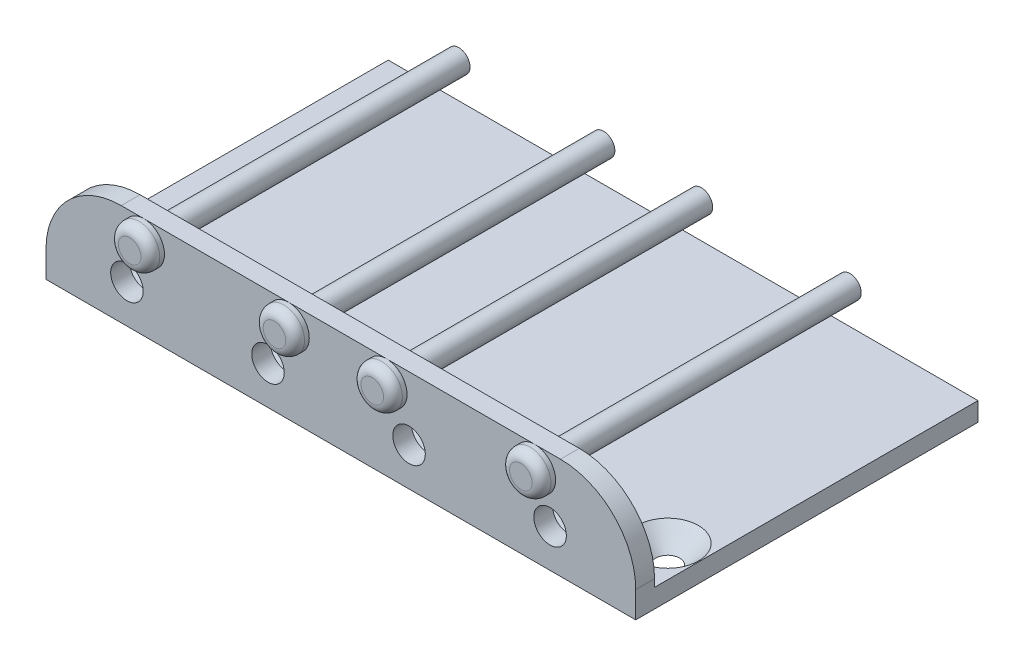
SolidWorks part; units mm, degrees
ref_plane "Front Plane" through (0, 0, 0) normal (0, 0, 1) x (1, 0, 0)
ref_plane "Top Plane" through (0, 0, 0) normal (0, 1, 0) x (1, 0, 0)
ref_plane "Right Plane" through (0, 0, 0) normal (1, 0, 0) x (0, 0, -1)
sketch "Sketch1" plane through (0, 0, 0) normal (0, 1, 0) x (1, 0, 0)
  line L1 (0, 0) -> (79.6544, 0)
  line L2 (0, 0) -> (0, 46.228)
  line L3 (0, 46.228) -> (79.6544, 46.228)
  line L4 (79.6544, 0) -> (79.6544, 46.228)
  dimension "D1" = 46.228
  dimension "D2" = 79.6544
extrude "Boss-Extrude1" add sketch "Sketch1" along normal blind 2.54
sketch "Sketch2" plane through (79.6544, 0, 0) normal (1, 0, 0) x (0, 0, -1)
  line L0 (0, 2.54) -> (0, 13.716)
  line L1 (0, 13.716) -> (2.54, 13.716)
  line L2 (2.54, 13.716) -> (2.54, 2.54)
  line L3 (0, 2.54) -> (46.228, 2.54) construction
  line L4 (2.54, 2.54) -> (0, 2.54)
  dimension "D1" = 2.54
  dimension "D2" = 11.176
extrude "Boss-Extrude2" add sketch "Sketch2" against normal up to surface (79.6544 mm away) up to face at (0, 1.27, -23.114)
sketch "Sketch3" plane through (0, 0, 0) normal (0, 0, 1) x (1, 0, 0)
  line L1 (0, 13.716) -> (79.6544, 13.716) construction
  line L2 (0, 13.716) -> (0, 0) construction
  circle A0 centre (10.9347, 5.1689) radius 2.1971
  circle A1 centre (29.9847, 5.1689) radius 2.1971
  circle A2 centre (49.0347, 5.1689) radius 2.1971
  circle A3 centre (68.0847, 5.1689) radius 2.1971
  point P9 (10.9347, 7.366)
  point P11 (8.7376, 5.1689)
  dimension "D1" = 4.3942
  dimension "D3" = 38.1
  dimension "D4" = 57.15
  dimension "D2" = 19.05
  dimension "D5" = 6.35
  dimension "D6" = 8.7376
extrude "Cut-Extrude1" cut sketch "Sketch3" against normal through all
sketch "Sketch4" plane through (0, 0, 0) normal (0, 0, 1) x (1, 0, 0)
  line L0 (0, 13.716) -> (0, 0) construction
  line L1 (0, 13.716) -> (79.6544, 13.716) construction
  circle A0 centre (13.208, 10.922) radius 2.794
  circle A1 centre (32.766, 10.922) radius 2.794
  circle A2 centre (45.974, 10.922) radius 2.794
  circle A3 centre (66.04, 10.922) radius 2.794
  point P9 (16.002, 10.922)
  point P11 (35.56, 10.922)
  point P16 (13.208, 8.128)
  dimension "D1" = 5.588
  dimension "D2" = 16.002
  dimension "D3" = 35.56
  dimension "D4" = 5.588
  dimension "D5" = 45.974
  dimension "D6" = 66.04
extrude "Boss-Extrude3" add sketch "Sketch4" along normal blind 1.905
fillet "Fillet1" radius 10.16 2 edges at (79.6544, 13.716, -1.27) (0, 13.716, -1.27)
fillet "Fillet2" radius 1.27 4 edges at (68.834, 10.922, 1.905) (48.768, 10.922, 1.905) (35.56, 10.922, 1.905) (16.002, 10.922, 1.905)
sketch "Sketch5" plane through (0, 0, -2.54) normal (0, 0, -1) x (-1, 0, 0)
  circle A0 centre (-66.04, 10.922) radius 1.524
  circle A1 centre (-45.974, 10.922) radius 1.524
  circle A2 centre (-32.766, 10.922) radius 1.524
  circle A3 centre (-13.208, 10.922) radius 1.524
  circle A4 centre (-66.04, 10.922) radius 2.794 construction
  circle A5 centre (-45.974, 10.922) radius 2.794 construction
  circle A6 centre (-32.766, 10.922) radius 2.794 construction
  circle A7 centre (-13.208, 10.922) radius 2.794 construction
  dimension "D1" = 3.048
extrude "Boss-Extrude4" add sketch "Sketch5" along normal offset from surface (40.005 mm away) 44.45 up to face at (67.564, 10.922, 1.905)
sketch "Sketch6" plane through (0, 0, 0) normal (0, -1, 0) x (1, 0, 0)
  line L0 (0, 0) -> (79.6544, 0) construction
  line L1 (39.8272, 0) -> (39.8272, -8.5915) construction
  line L2 (39.8272, -8.5915) -> (30.9583, -8.5915)
  circle A0 centre (39.8272, -8.5915) radius 1.6066
  circle A1 centre (22.0472, -8.5915) radius 1.6066
  circle A2 centre (4.2672, -8.5915) radius 1.6066
  circle A3 centre (57.6072, -8.5915) radius 1.6066
  circle A4 centre (75.3872, -8.5915) radius 1.6066
  point P2 (39.8272, -6.985)
  dimension "D1" = 3.2131
  dimension "D2" = 6.985
  dimension "D5" = 17.78
  dimension "D6" = 17.78
  dimension "D3" = 3
  dimension "D4" = 3
extrude "Cut-Extrude2" cut sketch "Sketch6" against normal up to surface (2.54 mm away) contours A0 L1 L2 | L1 A0 L2 | A3 | A1 | A2 | A4 region at (40.0545, 0, -8.8188) region at (39.1454, 0, -7.9097) region at (22.0472, 0, -8.5915) region at (4.2672, 0, -8.5915) region at (57.6072, 0, -8.5915) region at (75.3872, 0, -8.5915) up to face at (39.8272, 2.54, -24.384)
chamfer "Chamfer1" distance 2.54 angle 45 5 edges at (75.3872, 2.54, -10.1981) (57.6072, 2.54, -10.1981) (39.8272, 2.54, -10.1981) (4.2672, 2.54, -10.1981) (22.0472, 2.54, -10.1981)
